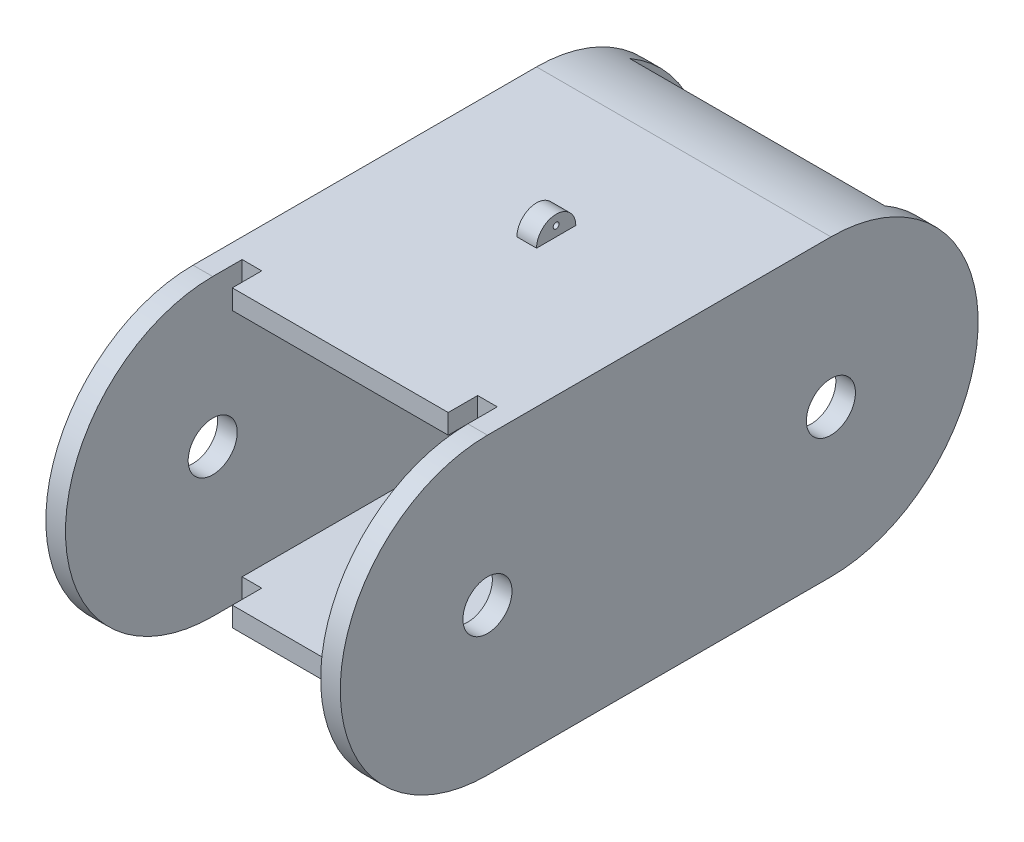
SolidWorks part; units mm, degrees
ref_plane "Front Plane" through (0, 0, 0) normal (0, 0, 1) x (1, 0, 0)
ref_plane "Top Plane" through (0, 0, 0) normal (0, 1, 0) x (1, 0, 0)
ref_plane "Right Plane" through (0, 0, 0) normal (1, 0, 0) x (0, 0, -1)
ref_plane "End Plane" through (0, 0, -31.75) normal (0, 0, 1) x (1, 0, 0)
ref_plane "Inside Plane" through (0, 19.05, 0) normal (0, 1, 0) x (1, 0, 0)
sketch "Sketch1" plane through (0, 0, 0) normal (0, 1, 0) x (1, 0, 0)
  line L1 (0, 0) -> (19.05, 0)
  line L2 (0, 0) -> (0, 41.275)
  line L3 (0, 41.275) -> (19.05, 41.275)
  line L4 (19.05, 0) -> (19.05, 41.275)
  dimension "D1" = 41.275
  dimension "D2" = 19.05
extrude "Boss-Extrude1" add sketch "Sketch1" along normal blind 19.05
sketch "Sketch2" plane through (0, 0, 0) normal (0, 0, 1) x (1, 0, 0)
  line L0 (0, 19.05) -> (19.05, 19.05) construction
  line L1 (1.27, 17.78) -> (17.78, 17.78)
  line L2 (1.27, 17.78) -> (1.27, 1.27)
  line L3 (1.27, 1.27) -> (17.78, 1.27)
  line L4 (17.78, 17.78) -> (17.78, 1.27)
  line L5 (0, 19.05) -> (0, 0) construction
  line L6 (0, 0) -> (19.05, 0) construction
  line L7 (19.05, 19.05) -> (19.05, 0) construction
  dimension "D1" = 1.27
  dimension "D2" = 1.27
  dimension "D3" = 1.27
  dimension "D4" = 1.27
extrude "Cut-Extrude1" cut sketch "Sketch2" against normal blind 50.8
sketch "Sketch3" plane through (0, 19.05, 0) normal (0, 1, 0) x (1, 0, 0)
  line L0 (0, 41.275) -> (0, 0) construction
  line L1 (8.89, 24.13) -> (10.16, 24.13)
  line L2 (8.89, 24.13) -> (8.89, 21.59)
  line L3 (8.89, 21.59) -> (10.16, 21.59)
  line L4 (10.16, 24.13) -> (10.16, 21.59)
  line L5 (0, 0) -> (19.05, 0) construction
  dimension "D1" = 1.27
  dimension "D2" = 8.89
  dimension "D3" = 21.59
  dimension "D4" = 2.54
extrude "Boss-Extrude2" add sketch "Sketch3" along normal blind 1.27
sketch "Sketch4" plane through (0, 0, 0) normal (1, 0, 0) x (0, 0, -1)
  line L0 (24.13, 19.05) -> (21.59, 19.05) construction
  line L1 (22.86, 20.32) -> (22.86, 19.685) construction
  line L2 (41.275, 19.05) -> (0, 19.05) construction
  line L3 (21.59, 20.32) -> (24.13, 20.32) construction
  line L4 (41.275, 0) -> (0, 0) construction
  line L5 (0, 19.05) -> (0, 0) construction
  circle A0 centre (22.86, 19.685) radius 0.1905
  arc A1 (24.13, 19.05) -> (21.59, 19.05) centre (22.86, 20.4483) ccw
  circle A4 centre (9.525, 9.525) radius 1.5875
  arc A6 (9.525, 19.05) -> (9.525, 0) centre (9.525, 9.525) ccw
  arc A7 (9.525, 19.05) -> (9.525, 0) centre (4.0998, 9.525) ccw
  ellipse E0 centre (22.86, 19.05) end of major axis (22.86, 20.32) minor radius 1.27 (24.13, 19.05) -> (21.59, 19.05) ccw
  point P15 (26.67, 20.32)
  dimension "D1" = 0.635
  dimension "D4" = 9.525
  dimension "D5" = 9.525
extrude "Cut-Extrude2" cut sketch "Sketch4" along normal blind 19.05
fillet "Fillet1" [suppressed] radius 0.635
fillet "Fillet2" [suppressed] radius 2.54
ref_plane "Mirror Plane" through (0, 0, -20.6375) normal (0, 0, 1) x (1, 0, 0)
mirror "Mirror1" about plane through (0, 0, -20.6375) normal (0, 0, 1) of "Cut-Extrude2"
sketch "Sketch7" plane through (0, 19.05, 0) normal (0, 1, 0) x (1, 0, 0)
  line L0 (2.54, 9.525) -> (16.51, 9.525)
  line L1 (1.27, 0) -> (2.54, 0)
  line L2 (1.27, 0) -> (1.27, 11.43)
  line L3 (1.27, 11.43) -> (2.54, 11.43)
  line L4 (2.54, 9.525) -> (2.54, 11.43)
  line L5 (17.78, 0) -> (16.51, 0)
  line L6 (17.78, 0) -> (17.78, 11.43)
  line L7 (17.78, 11.43) -> (16.51, 11.43)
  line L8 (16.51, 9.525) -> (16.51, 11.43)
  line L9 (19.05, 9.525) -> (0, 9.525) construction
  line L10 (2.54, 0) -> (16.51, 0)
  dimension "D1" = 1.27
  dimension "D2" = 1.27
  dimension "D3" = 11.43
  dimension "D4" = 11.43
extrude "Cut-Extrude3" cut sketch "Sketch7" against normal blind 25.4
